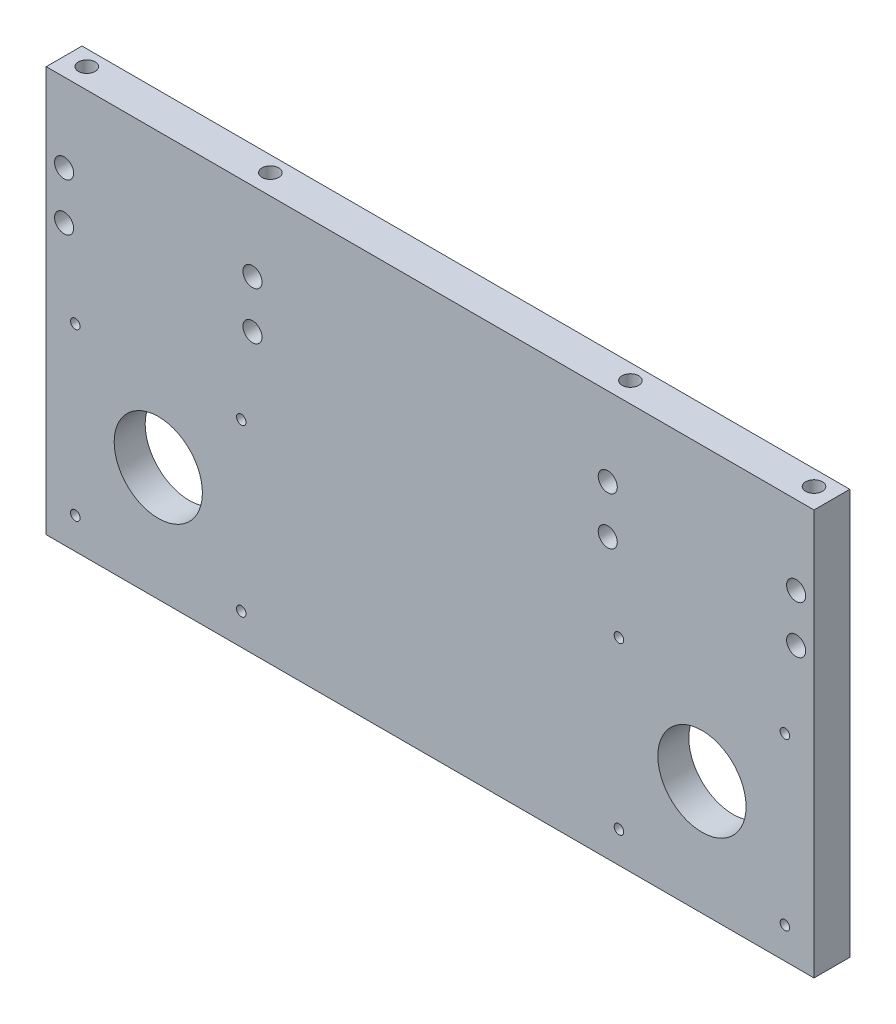
SolidWorks part; units mm, degrees
ref_plane "Płaszczyzna przednia" through (0, 0, 0) normal (0, 0, 1) x (1, 0, 0)
ref_plane "Płaszczyzna górna" through (0, 0, 0) normal (0, 1, 0) x (1, 0, 0)
ref_plane "Płaszczyzna prawa" through (0, 0, 0) normal (1, 0, 0) x (0, 0, -1)
sketch "Szkic1" plane through (0, 0, 0) normal (0, 0, 1) x (1, 0, 0)
  line L1 (161, -85) -> (-161, -85)
  line L2 (161, -85) -> (161, 85)
  line L3 (161, 85) -> (-161, 85)
  line L4 (-161, -85) -> (-161, 85)
  line L5 (161, -85) -> (-161, 85) construction
  line L6 (161, 85) -> (-161, -85) construction
  point P0 (0, 0)
  dimension "D1" = 322
  dimension "D2" = 170
extrude "Dodanie-wyciągnięcie1" add sketch "Szkic1" along normal blind 15
sketch "Szkic2" plane through (0, 0, 15) normal (0, 0, 1) x (1, 0, 0)
  line L2 (-161, -85) -> (161, -85) construction
  line L7 (-161, 85) -> (-161, -85) construction
  circle A1 centre (-148.8, -71.87) radius 2
  dimension "D1" = 13.13
  dimension "D2" = 12.2
  dimension "D5" = 4
extrude "Wytnij-wyciągnięcie2" cut sketch "Szkic2" against normal blind 17.75 contours A1 region at (-148.8, -71.87, 15)
pattern_linear "Szyk liniowy1" count 2 spacing 69.6 along (1, 0, 0) count 2 spacing 69.6 along (0, 1, 0) of "Wytnij-wyciągnięcie2"
sketch "Szkic5" plane through (0, 0, 0) normal (0, 0, -1) x (-1, 0, 0)
  line L1 (161, -85) -> (-161, -85) construction
  line L2 (161, 85) -> (161, -85) construction
  circle A1 centre (114, -37.07) radius 37.5
  dimension "D1" = 47.93
  dimension "D5" = 75
  dimension "D2" = 47
extrude "Wytnij-wyciągnięcie3" cut sketch "Szkic5" against normal blind 2 contours A1 region at (-114, -37.07, 0)
sketch "Szkic7" plane through (0, 0, 2) normal (0, 0, -1) x (-1, 0, 0)
  circle A3 centre (114, -37.07) radius 18.5
  dimension "D1" = 37
extrude "Wytnij-wyciągnięcie4" cut sketch "Szkic7" against normal blind 17.75 contours A3 region at (-114, -37.07, 2)
sketch "Szkic10" plane through (0, 0, 15) normal (0, 0, 1) x (1, 0, 0)
  line L0 (161, 85) -> (-161, 85) construction
  line L1 (-161, 85) -> (-161, -85) construction
  circle A0 centre (-153.5, 52) radius 4
  circle A1 centre (-153.5, 32) radius 4
  dimension "D1" = 53
  dimension "D3" = 8
  dimension "D4" = 8
  dimension "D2" = 20
  dimension "D5" = 7.5
extrude "Wytnij-wyciągnięcie7" cut sketch "Szkic10" against normal through all
pattern_linear "Szyk liniowy3" count 2 spacing 79 along (1, 0, 0) of "Wytnij-wyciągnięcie7"
pattern_linear "Szyk liniowy2" count 2 spacing 228 along (1, 0, 0) of "Wytnij-wyciągnięcie2", "Szyk liniowy1", "Wytnij-wyciągnięcie3", "Wytnij-wyciągnięcie4", "Szyk liniowy3"
sketch "Szkic8" plane through (0, 85, 0) normal (0, 1, 0) x (1, 0, 0)
  line L0 (-161, -15) -> (-161, 0) construction
  line L1 (161, -15) -> (-161, -15) construction
  line L2 (161, -15) -> (161, 0) construction
  line L3 (161, -15) -> (-161, -15) construction
  circle A0 centre (-153.8, -6.5) radius 4
  circle A1 centre (153.8, -6.5) radius 4
  dimension "D1" = 7.2
  dimension "D3" = 8
  dimension "D6" = 8
  dimension "D2" = 8.5
  dimension "D4" = 7.2
  dimension "D5" = 8.5
extrude "Wytnij-wyciągnięcie5" [suppressed] cut sketch "Szkic8" against normal blind 20
sketch "Szkic11" plane through (0, 0, 15) normal (0, 0, 1) x (1, 0, 0)
  line L0 (161, 85) -> (-161, 85) construction
  line L1 (161, -85) -> (161, 85) construction
  circle A0 centre (153.5, 32) radius 4
  circle A1 centre (153.5, 52) radius 4
  dimension "D1" = 53
  dimension "D2" = 8
  dimension "D3" = 8
  dimension "D4" = 7.5
  dimension "D5" = 20
extrude "Wytnij-wyciągnięcie8" [suppressed] cut sketch "Szkic11" against normal through all
hole_wizard "Otwór gwintowany M8x1.01" positions "Szkic12" profile "Szkic13" tap size "M8x1.0" standard "Ansi Metric"
sketch "Szkic12" plane through (0, 85, 0) normal (0, 1, 0) x (1, 0, 0)
  line L0 (-161, -6.5) -> (161, -6.5) construction
  line L1 (-161, -15) -> (-161, 0) construction
  line L2 (161, -15) -> (161, 0) construction
  line L5 (161, -15) -> (-161, -15) construction
  point P0 (-152.5, -6.5)
  point P2 (-75.5, -6.5)
  point P4 (75.5, -6.5)
  point P6 (152.5, -6.5)
  dimension "D1" = 8.5
  dimension "D2" = 8.5
  dimension "D3" = 8.5
  dimension "D4" = 77
  dimension "D5" = 77
sketch "Szkic13" plane through (-152.5, 85, 6.5) normal (1, 0, 0) x (0, 0, 1)
  line L0 (0, 0) -> (0, 23.103)
  line L1 (0, 23.103) -> (3.5, 21)
  line L2 (3.5, 21) -> (3.5, 0)
  line L5 (3.5, 0) -> (0, 0)
  line L10 (0, 23.103) -> (-3.5, 21) construction
  line L11 (0, -6.35) -> (0, 107.95) construction
  dimension "Średnica wiertła gwintu" = 7
  dimension "Głębokość otworu gwintowanego" = 21
  dimension "Kąt wiertła" = 118
cosmetic thread "Gwint otworu1" parameters "D1"=16, "D2"=8
cosmetic thread "Gwint otworu2" parameters "D1"=16, "D2"=8
cosmetic thread "Gwint otworu3" parameters "D1"=16, "D2"=8
cosmetic thread "Gwint otworu4" parameters "D1"=16, "D2"=8
